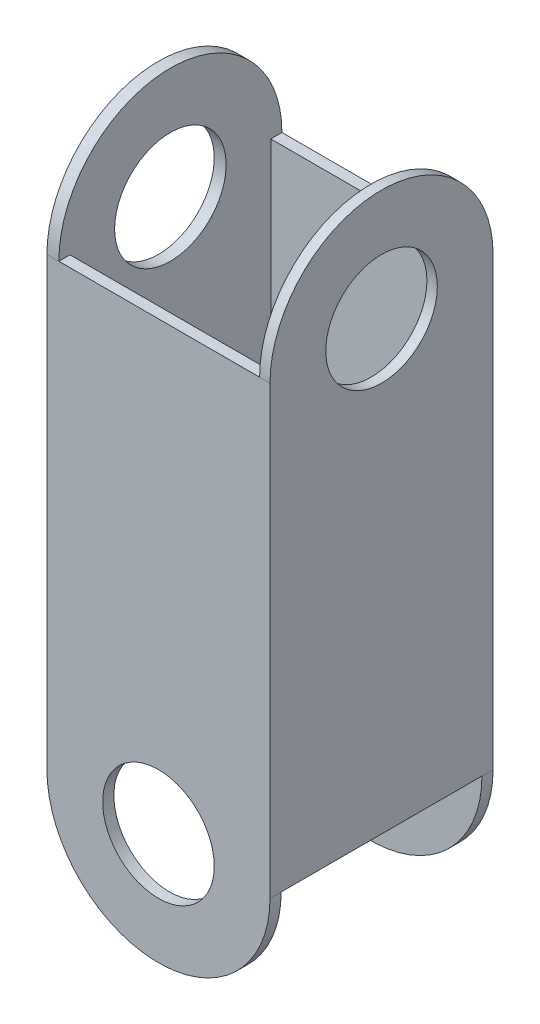
SolidWorks part; units mm, degrees
ref_plane "Front Plane" through (0, 0, 0) normal (0, 0, 1) x (1, 0, 0)
ref_plane "Top Plane" through (0, 0, 0) normal (0, 1, 0) x (1, 0, 0)
ref_plane "Right Plane" through (0, 0, 0) normal (1, 0, 0) x (0, 0, -1)
sketch "Sketch1" plane through (0, 0, 0) normal (1, 0, 0) x (0, 0, -1)
  line L0 (-10, 20) -> (10, 20)
  line L2 (-10, 20) -> (-10, -20)
  line L3 (-10, -20) -> (10, -20)
  line L4 (10, 20) -> (10, -20)
  line L5 (-10, 20) -> (10, -20) construction
  line L6 (-10, -20) -> (10, 20) construction
  point P0 (0, 0)
  dimension "D1" = 20
extrude "Boss-Extrude1" add sketch "Sketch1" along normal blind 20
sketch "Sketch2" plane through (0, 0, 10) normal (0, 0, 1) x (1, 0, 0)
  line L0 (20, -20) -> (0, -20) construction
  circle A0 centre (10, -20) radius 10
  circle A1 centre (10, -20) radius 5
sketch "Sketch3" plane through (0, -20, 0) normal (0, -1, 0) x (1, 0, 0)
  line L1 (0.966, 9) -> (18.966, 9)
  line L2 (0.966, 9) -> (0.966, -9)
  line L3 (0.966, -9) -> (18.966, -9)
  line L4 (18.966, 9) -> (18.966, -9)
  line L5 (0.966, 9) -> (18.966, -9) construction
  line L6 (0.966, -9) -> (18.966, 9) construction
  point P0 (9.966, 0)
  point P5 (9.966, 0)
extrude "Cut-Extrude1" cut sketch "Sketch3" against normal blind 20
extrude "Boss-Extrude2" add sketch "Sketch2" against normal up to vertex (1 mm away) contours A0 up to point (0.966, -20, 9)
sketch "Sketch4" plane through (0, 0, -10) normal (0, 0, -1) x (-1, 0, 0)
  line L0 (-20, -20) -> (0, -20) construction
  circle A0 centre (-10, -20) radius 10
  circle A1 centre (-10, -20) radius 5
extrude "Boss-Extrude3" add sketch "Sketch4" against normal up to vertex (1 mm away) up to point (18.966, -20, -9)
sketch "Sketch5" plane through (0, 20, 0) normal (0, 1, 0) x (1, 0, 0)
  line L1 (1.0681, 9) -> (19.0681, 9)
  line L2 (1.0681, 9) -> (1.0681, -9)
  line L3 (1.0681, -9) -> (19.0681, -9)
  line L4 (19.0681, 9) -> (19.0681, -9)
  line L5 (1.0681, 9) -> (19.0681, -9) construction
  line L6 (1.0681, -9) -> (19.0681, 9) construction
  point P0 (10.0681, 0)
extrude "Cut-Extrude3" cut sketch "Sketch5" against normal blind 18
sketch "Sketch7" plane through (0, 0, 0) normal (-1, 0, 0) x (0, 0, 1)
  line L0 (-10, 20) -> (10, 20) construction
  circle A0 centre (0, 20) radius 10
  circle A1 centre (0, 20) radius 5
sketch "Sketch8" plane through (20, 0, 0) normal (1, 0, 0) x (0, 0, -1)
  circle A0 centre (0, 20) radius 10
  circle A1 centre (0, 20) radius 5
extrude "Boss-Extrude4" add sketch "Sketch8" against normal up to vertex (0.9319 mm away) up to point (19.0681, 20, 9)
extrude "Boss-Extrude5" add sketch "Sketch7" against normal up to vertex (1.0681 mm away) contours A0 up to point (1.0681, 20, -9)
sketch "Sketch11" plane through (0, 0, 0) normal (-1, 0, 0) x (0, 0, 1)
  line L0 (-26.0355, 20) -> (20.1137, 20) construction
  circle A0 centre (0, 20) radius 5
  point P5 (0, 0)
extrude "Cut-Extrude4" cut sketch "Sketch11" against normal through all
sketch "Sketch12" plane through (0, 0, 10) normal (0, 0, 1) x (1, 0, 0)
  line L0 (0, -20) -> (29.1948, -20) construction
  line L1 (10, -30) -> (10, -6.1771) construction
  arc A0 (0, -20) -> (20, -20) centre (10, -20) ccw construction
  circle A1 centre (10, -20) radius 5
extrude "Cut-Extrude5" cut sketch "Sketch12" against normal through all
